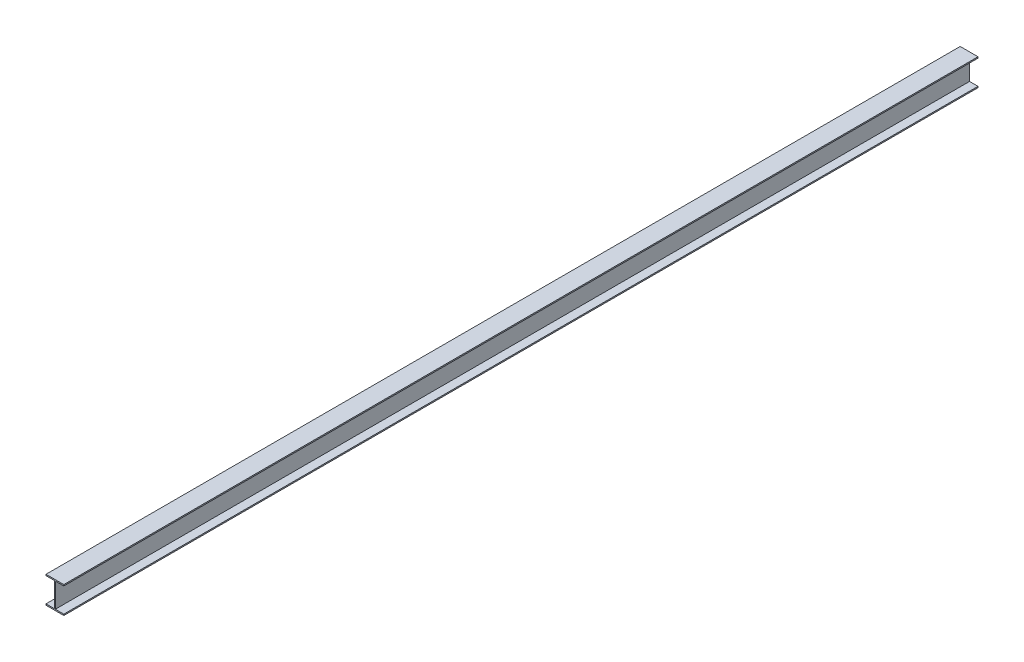
SolidWorks part; units mm, degrees
material "ASTM A992 Steel"
ref_plane "Front" through (0, 0, 0) normal (0, 0, 1) x (1, 0, 0)
ref_plane "Top" through (0, 0, 0) normal (0, 1, 0) x (1, 0, 0)
ref_plane "Right" through (0, 0, 0) normal (1, 0, 0) x (0, 0, -1)
sketch "Sketch1" plane through (0, 0, 0) normal (0, 0, 1) x (1, 0, 0)
  line L0 (0, -0.0002) -> (101.6, -0.0002)
  line L1 (101.6, -0.0002) -> (101.6, -7.1122)
  line L2 (101.6, -7.1122) -> (53.408, -7.1122)
  line L3 (53.408, -7.1122) -> (53.408, -146.0502)
  line L4 (53.408, -146.0502) -> (101.6, -146.0502)
  line L5 (101.6, -146.0502) -> (101.6, -153.1622)
  line L6 (101.6, -153.1622) -> (0, -153.1622)
  line L7 (0, -153.1622) -> (0, -146.0502)
  line L8 (0, -146.0502) -> (47.566, -146.0502)
  line L9 (47.566, -146.0502) -> (47.566, -7.1122)
  line L10 (47.566, -7.1122) -> (0, -7.1122)
  line L11 (0, -7.1122) -> (0, -0.0002)
  line L12 (50.8, -0.0002) -> (50.8, -153.1622) construction
  dimension "D1" = 5.842
  dimension "D2" = 7.112
  dimension "D3" = 7.112
  dimension "D4" = 7.112
  dimension "D5" = 153.162
  dimension "D6" = 50.8
  dimension "D7" = 50.8
  dimension "D8" = 47.566
extrude "Boss-Extrude1" add sketch "Sketch1" along normal blind 5214.4
sketch "Sketch2" plane through (0, -153.1622, 0) normal (0, -1, 0) x (1, 0, 0)
  line L0 (0, 5214.4) -> (0, 0) construction
  line L1 (101.6, 5214.4) -> (101.6, 0) construction
  line L3 (101.6, 2607.2) -> (101.6, 2759.6)
  line L4 (101.6, 2759.6) -> (-279.5172, 2759.6)
  line L5 (-279.5172, 2607.2) -> (-279.5172, 2759.6)
  line L8 (101.6, 2607.2) -> (101.6, 2454.8)
  line L9 (101.6, 2454.8) -> (-279.5172, 2454.8)
  line L10 (-279.5172, 2607.2) -> (-279.5172, 2454.8)
  point P0 (0, 2607.2)
  dimension "D1" = 152.4
  dimension "D2" = 152.4
split line "Split Line1"
